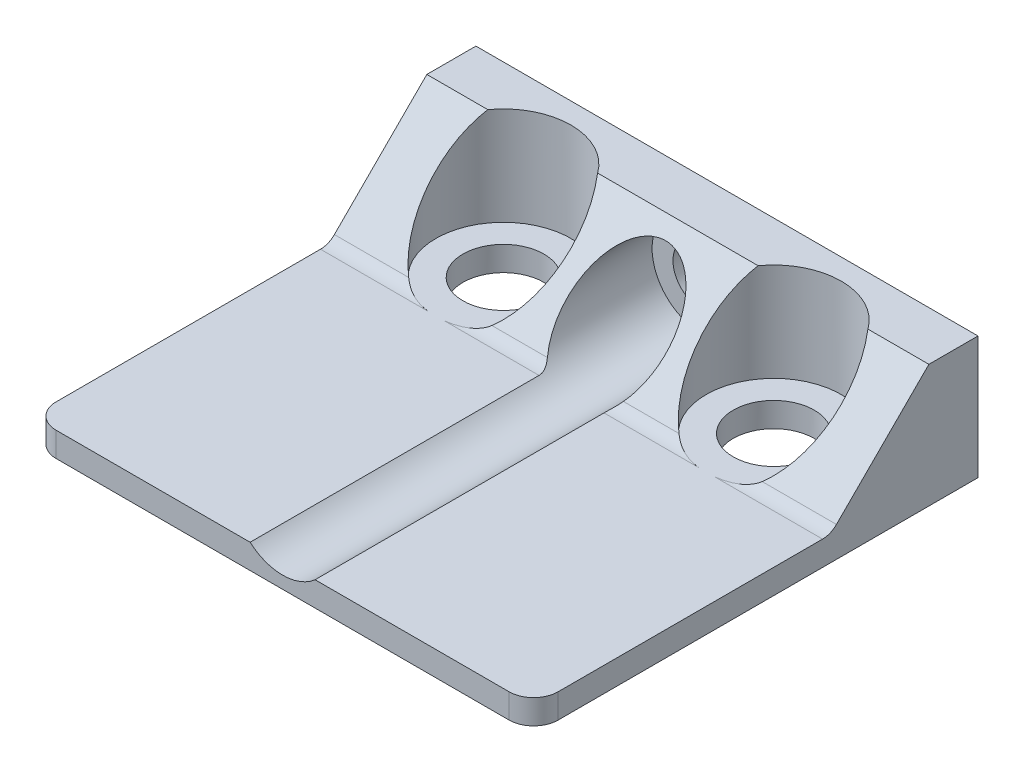
SolidWorks part; units mm, degrees
ref_plane "Front Plane" through (0, 0, 0) normal (0, 0, 1) x (1, 0, 0)
ref_plane "Top Plane" through (0, 0, 0) normal (0, 1, 0) x (1, 0, 0)
ref_plane "Right Plane" through (0, 0, 0) normal (1, 0, 0) x (0, 0, -1)
sketch "Sketch1" plane through (0, 0, 0) normal (0, 1, 0) x (1, 0, 0)
  line L1 (-10.225, -9.05) -> (10.225, -9.05)
  line L2 (-10.225, -9.05) -> (-10.225, 9.05)
  line L3 (-10.225, 9.05) -> (10.225, 9.05)
  line L4 (10.225, -9.05) -> (10.225, 9.05)
  line L5 (-10.225, -9.05) -> (10.225, 9.05) construction
  line L6 (-10.225, 9.05) -> (10.225, -9.05) construction
  point P0 (0, 0)
  dimension "D1" = 20.45
  dimension "D2" = 18.1
extrude "Boss-Extrude2" add sketch "Sketch1" along normal blind 1
sketch "Sketch3" plane through (0, 0, 0) normal (1, 0, 0) x (0, 0, -1)
  line L0 (9.05, 1) -> (9.05, 5)
  line L1 (9.05, 1) -> (3.05, 1)
  line L3 (9.05, 5) -> (7.05, 5)
  line L4 (-9.05, 1) -> (9.05, 1) construction
  line L5 (3.05, 1) -> (7.05, 5)
  dimension "D1" = 6
  dimension "D2" = 4
  dimension "D3" = 2
extrude "Boss-Extrude3" add sketch "Sketch3" along normal up to surface and the other way up to surface up to face at (10.225, 0.5, 0) other way up to face at (-10.225, 0.5, 0)
ref_plane "Plane5" through (0, 5, 0) normal (0, 1, 0) x (1, 0, 0)
sketch "Sketch4" plane through (0, 5, 0) normal (0, 1, 0) x (1, 0, 0)
  line L0 (-10.225, 3.05) -> (-10.225, 7.05) construction
  line L1 (10.225, 9.05) -> (-10.225, 9.05) construction
  line L2 (10.225, 3.05) -> (10.225, 7.05) construction
  circle A0 centre (-5.505, 5.45) radius 1.65
  circle A1 centre (5.505, 5.45) radius 1.65
  dimension "D5" = 3.3
  dimension "D6" = 3.3
  dimension "D1" = 4.72
  dimension "D2" = 3.6
  dimension "D3" = 3.6
  dimension "D4" = 4.72
extrude "Cut-Extrude1" cut sketch "Sketch4" against normal up to surface (5 mm away) up to face at (0, 0, 0)
sketch "Sketch6" plane through (0, 5, 0) normal (0, 1, 0) x (1, 0, 0)
  circle A0 centre (-5.505, 5.45) radius 2.75
  circle A1 centre (5.505, 5.45) radius 2.75
  dimension "D1" = 5.5
  dimension "D2" = 5.5
extrude "Cut-Extrude2" cut sketch "Sketch6" against normal blind 4
sketch "Sketch7" plane through (0, 0, 0) normal (0, 0, 1) x (1, 0, 0)
  line L0 (3.2684, 5) -> (-3.2684, 5) construction
  line L1 (-10.225, 1) -> (-10.225, 5) construction
  circle A0 centre (0, 2.5) radius 1.15
  dimension "D3" = 2.3
  dimension "D1" = 2.5
  dimension "D2" = 10.225
extrude "Cut-Extrude3" cut sketch "Sketch7" against normal up to surface (9.05 mm away) up to face at (0, 2.5, -9.05)
sketch "Sketch8" plane through (0, 0, 0) normal (0, 0, 1) x (1, 0, 0)
  circle A0 centre (0, 2.5) radius 2
  dimension "D1" = 4
extrude "Cut-Extrude4" cut sketch "Sketch8" against normal blind 8 and the other way up to surface (9.05 mm away) other way up to face at (0, 0.5, 9.05)
fillet "Fillet2" radius 1 2 edges at (10.225, 0.5, 9.05) (-10.225, 0.5, 9.05)
fillet "Fillet3" radius 0.8 4 edges at (-8.5363, 1, -3.05) (-2.7427, 1, -3.05) (2.7427, 1, -3.05) (8.5363, 1, -3.05)
